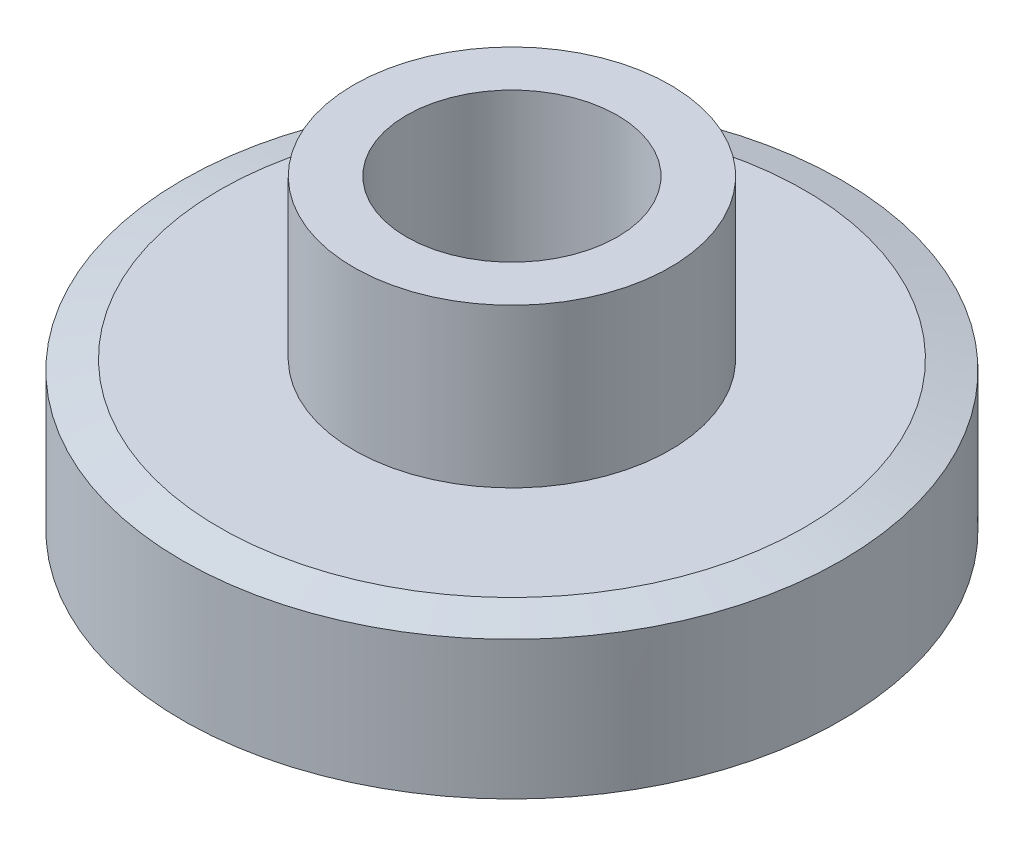
SolidWorks part; units mm, degrees
material "Сталь ШХ15 ГОСТ 801-78"
ref_plane "Plane1" through (0, 0, 0) normal (0, 0, 1) x (1, 0, 0)
ref_plane "Plane2" through (0, 0, 0) normal (0, 1, 0) x (1, 0, 0)
ref_plane "Plane3" through (0, 0, 0) normal (1, 0, 0) x (0, 0, -1)
sketch "Эскиз2" plane through (0, 0, 0) normal (0, 0, 1) x (1, 0, 0)
  line L0 (0, 0) -> (6.25, 0)
  line L1 (6.25, 0) -> (6.25, 3)
  line L2 (6.25, 3) -> (3, 3)
  line L3 (3, 3) -> (3, 6)
  line L4 (3, 6) -> (0, 6)
  line L5 (0, 6) -> (0, 0)
  dimension "D1" = 6.25
  dimension "D2" = 3
  dimension "D3" = 3
  dimension "D4" = 3
ref_axis "Ось1" through (0, 6, 0) along (0, -1, 0)
revolve "Повернуть2" add sketch "Эскиз2" angle 360 about axis through (0, 6, 0) along (0, -1, 0)
chamfer "Фаска2" distance 0.705 angle 15 1 edges at (-6.25, 3, 0) first distance on face at (-3, 3, 0)
chamfer "Фаска3" distance 0.705 angle 15 1 edges at (-6.25, 0, 0) first distance on face at (-6.25, 0, 0)
sketch "Эскиз4" plane through (0, 6, 0) normal (0, 1, 0) x (1, 0, 0)
  circle A0 centre (0, 0) radius 2
  dimension "D1" = 4
extrude "Вырез-Вытянуть2" cut sketch "Эскиз4" against normal through all both contours A0
